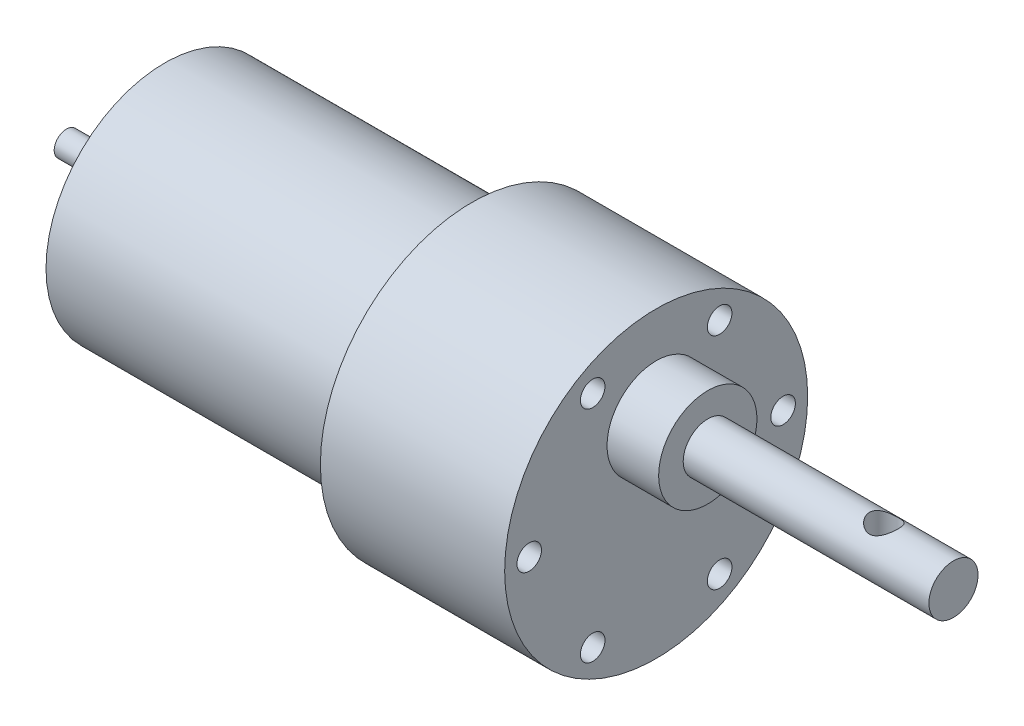
SolidWorks part; units mm, degrees
ref_plane "Front Plane" through (0, 0, 0) normal (0, 0, 1) x (1, 0, 0)
ref_plane "Top Plane" through (0, 0, 0) normal (0, 1, 0) x (1, 0, 0)
ref_plane "Right Plane" through (0, 0, 0) normal (1, 0, 0) x (0, 0, -1)
sketch "Sketch2" plane through (0, 0, 0) normal (0, 0, 1) x (1, 0, 0)
  line L0 (-31.2669, 14.5) -> (108.3035, 14.5) construction
  line L1 (0, 0) -> (37.5, 0)
  line L2 (0, 0) -> (0, 29)
  line L3 (0, 29) -> (37.5, 29)
  line L4 (37.5, 0) -> (37.5, 29)
  line L5 (37.5, 33) -> (60, 33)
  line L6 (37.5, 33) -> (37.5, -4)
  line L7 (37.5, -4) -> (60, -4)
  line L8 (60, 33) -> (60, -4)
  line L9 (60, 21.5) -> (124.844, 21.5) construction
  line L10 (0, 19.5) -> (-3, 19.5)
  line L11 (0, 19.5) -> (0, 9.5)
  line L12 (0, 9.5) -> (-3, 9.5)
  line L13 (-3, 19.5) -> (-3, 9.5)
  line L14 (0, 16) -> (-12, 16)
  line L15 (0, 16) -> (0, 13)
  line L16 (0, 13) -> (-12, 13)
  line L17 (-12, 16) -> (-12, 13)
  line L18 (-12, 14.5) -> (60, 14.5)
  line L19 (60, 27.5) -> (66.3, 27.5)
  line L20 (60, 27.5) -> (60, 15.5)
  line L21 (60, 15.5) -> (66.3, 15.5)
  line L22 (66.3, 27.5) -> (66.3, 15.5)
  line L23 (66.3, 24.5) -> (96.3, 24.5)
  line L24 (66.3, 24.5) -> (66.3, 18.5)
  line L25 (66.3, 18.5) -> (96.3, 18.5)
  line L26 (96.3, 24.5) -> (96.3, 18.5)
  line L27 (60, 21.5) -> (96.3, 21.5)
  point P15 (-3, 14.5)
  point P20 (-12, 14.5)
  point P27 (66.3, 21.5)
  point P32 (96.3, 21.5)
  dimension "D1" = 37.5
  dimension "D2" = 29
  dimension "D3" = 22.5
  dimension "D4" = 37
  dimension "D5" = 14.5
  dimension "D6" = 18.5
  dimension "D7" = 10
  dimension "D8" = 3
  dimension "D9" = 12
  dimension "D10" = 3
  dimension "D11" = 7
  dimension "D12" = 6.3
  dimension "D13" = 12
  dimension "D14" = 30
  dimension "D15" = 6
revolve "Revolve2" add sketch "Sketch2" angle 360 about L0 region at (18.75, 21.75, 0) region at (48.75, 23.75, 0) region at (-1.5, 15.25, 0) region at (-1.5, 17.75, 0) region at (-7.5, 15.25, 0)
revolve "Revolve3" add sketch "Sketch2<6>" angle 360 about L9 region at (63.15, 24.5, 0) region at (81.3, 23, 0)
sketch "Sketch2<6>" plane through (0, 0, 0) normal (0, 0, 1) x (1, 0, 0) same geometry as "Sketch2"
sketch "Sketch3" plane through (60, 0, 0) normal (1, 0, 0) x (0, 0, -1)
  line L0 (-18.5, 14.5) -> (18.5, 14.5) construction
  circle A0 centre (0, 14.5) radius 15.5 construction
  circle A1 centre (0, 14.5) radius 18.5 construction
  circle A3 centre (-15.5, 14.5) radius 1.5
  circle A4 centre (-7.75, 27.9234) radius 1.5
  circle A5 centre (7.75, 27.9234) radius 1.5
  circle A6 centre (15.5, 14.5) radius 1.5
  circle A7 centre (7.75, 1.0766) radius 1.5
  circle A8 centre (-7.75, 1.0766) radius 1.5
  point P21 (0, 14.5)
  dimension "D1" = 31
  dimension "D2" = 3
  dimension "D3" = 6
extrude "Cut-Extrude1" cut sketch "Sketch3" against normal blind 3.5
sketch "Sketch4" plane through (0, 0, 0) normal (0, 1, 0) x (1, 0, 0)
  line L0 (96.3, -3) -> (96.3, 3) construction
  line L1 (96.3, 3) -> (66.3, 3) construction
  circle A0 centre (87.8, 0) radius 1.75
  dimension "D2" = 3.5
  dimension "D1" = 8.5
  dimension "D3" = 3
extrude "Cut-Extrude2" cut sketch "Sketch4" along normal through all
